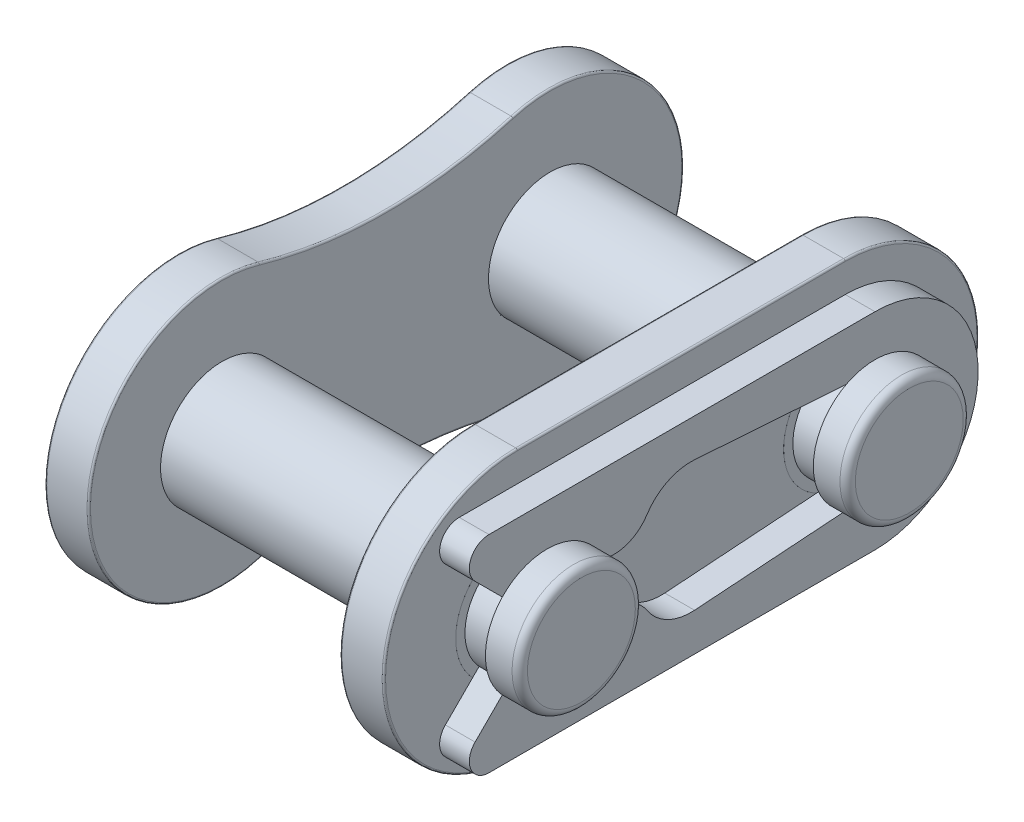
SolidWorks part; units mm, degrees
ref_plane "Front Plane" through (0, 0, 0) normal (0, 0, 1) x (1, 0, 0)
ref_plane "Top Plane" through (0, 0, 0) normal (0, 1, 0) x (1, 0, 0)
ref_plane "Right Plane" through (0, 0, 0) normal (1, 0, 0) x (0, 0, -1)
sketch "Sketch1" plane through (0, 0, 0) normal (1, 0, 0) x (0, 0, -1)
  line L0 (-4.7625, 0) -> (4.7625, 0) construction
  line L1 (-4.7625, 4.4069) -> (-4.7625, -4.4069) construction
  line L2 (4.7625, 4.4069) -> (4.7625, -4.4069) construction
  circle A0 centre (-4.7625, 0) radius 2.54 construction
  circle A1 centre (4.7625, 0) radius 2.54 construction
  circle A2 centre (-4.7625, 0) radius 1.7907 construction
  circle A3 centre (4.7625, 0) radius 1.7907 construction
  point P4 (0, 0)
  point P10 (-4.7625, 0)
  point P14 (4.7625, 0)
  dimension "For Roller Diameter" = 5.08
  dimension "Pin Diameter" = 3.5814
  dimension "For Plate Height" = 8.8138
  dimension "Pitch" = 9.525
sketch "Sketch2" plane through (0, 0, 0) normal (0, 1, 0) x (1, 0, 0)
  line L0 (-2.3812, 0) -> (2.3812, 0) construction
  line L1 (0, 4.7625) -> (6.7818, 4.7625) construction
  line L2 (0, 4.7625) -> (-5.9182, 4.7625) construction
  point P0 (-3.6513, 0)
  point P3 (0, 0)
  point P4 (3.6513, 0)
  dimension "For Roller Width" = 4.7625
  dimension "Plate Thickness" = 1.27
  dimension "Length L2" = 6.7818
  dimension "Length L1" = 5.9182
sketch "Sketch3" plane through (0, 0, 0) normal (1, 0, 0) x (0, 0, -1)
  line L0 (-4.7625, 3.8781) -> (-4.7625, -3.8781) construction
  line L1 (-4.7625, 3.8781) -> (4.7625, 3.8781)
  line L2 (-4.7625, -3.8781) -> (4.7625, -3.8781)
  arc A4 (-4.7625, 3.8781) -> (-4.7625, -3.8781) centre (-4.7625, 0) ccw
  arc A5 (4.7625, -3.8781) -> (4.7625, 3.8781) centre (4.7625, 0) ccw
  circle A8 centre (-4.7625, 0) radius 1.7907
  circle A9 centre (4.7625, 0) radius 1.7907
  circle A10 centre (-4.7625, 0) radius 1.7907 construction
  point P14 (0, 0)
  dimension "D1" = 7.7561
extrude "Boss-Extrude1" add sketch "Sketch3" along normal blind 1.27 from vertex starting at point (3.6513, 0, 0)
fillet "Fillet1" radius 0.0508 8 edges at (4.9213, 0, -8.6406) (3.6513, 0, -8.6406) (4.9213, 0, 8.6406) (3.6513, 0, 8.6406) (4.9213, 3.8781, 0) (4.9213, -3.8781, 0) (3.6513, 3.8781, 0) (3.6513, -3.8781, 0)
sketch "Sketch4" plane through (0, 0, 0) normal (1, 0, 0) x (0, 0, -1)
  line L0 (0, 3.1956) -> (0, -3.1956) construction
  line L1 (0, 3.7459) -> (0, -3.7459) construction
  circle A0 centre (-4.7625, 0) radius 1.7907
  circle A1 centre (4.7625, 0) radius 1.7907
  circle A2 centre (-4.7625, 0) radius 1.7907 construction
  circle A3 centre (4.7625, 0) radius 1.7907 construction
  arc A4 (-3.6734, 3.722) -> (-3.6734, -3.722) centre (-4.7625, 0) ccw
  arc A5 (3.6734, -3.722) -> (3.6734, 3.722) centre (4.7625, 0) ccw
  arc A6 (-4.7625, 3.8781) -> (-4.7625, -3.8781) centre (-4.7625, 0) ccw construction
  arc A7 (4.7625, -3.8781) -> (4.7625, 3.8781) centre (4.7625, 0) ccw construction
  arc A8 (-3.6734, 3.722) -> (3.6734, 3.722) centre (0, 16.2752) ccw
  arc A9 (-3.6734, -3.722) -> (3.6734, -3.722) centre (0, -16.2752) cw
  circle A10 centre (-4.7625, 0) radius 4.4069 construction
  circle A11 centre (4.7625, 0) radius 4.4069 construction
  arc A12 (-3.5623, 4.2403) -> (3.5623, 4.2403) centre (0, 16.8255) ccw construction
  arc A13 (-3.5623, -4.2403) -> (3.5623, -4.2403) centre (0, -16.8255) cw construction
  point P26 (0, 0)
  dimension "D1" = 7.4917
extrude "Boss-Extrude2" add sketch "Sketch4" against normal blind 1.27 from vertex separate body starting at point (-3.6513, 0, 0)
fillet "Fillet2" radius 0.0508 8 edges at (-4.9213, 3.1956, 0) (-4.9213, 0, -8.6406) (-4.9213, -3.1956, 0) (-3.6513, 3.1956, 0) (-3.6513, 0, -8.6406) (-3.6513, -3.1956, 0) (-4.9213, 0, 8.6406) (-3.6513, 0, 8.6406)
sketch "Sketch5" plane through (0, 0, 0) normal (1, 0, 0) x (0, 0, -1)
  circle A0 centre (-4.7625, 0) radius 1.7907
  circle A1 centre (4.7625, 0) radius 1.7907
  circle A2 centre (-4.7625, 0) radius 1.7907 construction
  circle A3 centre (4.7625, 0) radius 1.7907 construction
extrude "Boss-Extrude3" add sketch "Sketch5" along normal up to vertex (6.7818 mm away) and the other way up to vertex (5.9182 mm away) separate body up to point (6.7818, 0, -4.7625) other way up to point (-5.9182, 0, -4.7625)
fillet "Fillet3" radius 0.4477 1 edges at (-5.9182, 0, 2.9718)
fillet "Fillet4" radius 0.4477 1 edges at (-5.9182, 0, -6.5532)
sketch "Sketch6" plane through (0, 0, 0) normal (0, 1, 0) x (1, 0, 0)
  line L0 (-5.9182, -4.7625) -> (-4.9212, -4.7625) construction
  line L1 (-4.9212, -4.7625) -> (-3.6513, -4.7625) construction
  dimension "D2" = 0.9969
sketch "Sketch7" plane through (4.9213, 0, 0) normal (1, 0, 0) x (0, 0, -1)
  line L0 (4.7625, -2.9967) -> (-6.4493, -2.9967)
  line L1 (-6.8529, -2.0223) -> (-5.8723, -1.0417)
  line L2 (4.7625, 2.9967) -> (-6.4493, 2.9967)
  line L3 (-6.8529, 2.0223) -> (-5.8723, 1.0417)
  line L5 (-0.4791, 1.8923) -> (4.8687, 1.5184)
  line L6 (4.8687, -1.5184) -> (-0.4791, -1.8923)
  line L8 (4.7625, 0) -> (-4.7625, 0) construction
  line L9 (-5.8723, 1.0417) -> (-0.9254, 1.0417) construction
  arc A0 (4.7625, -2.9967) -> (4.7625, 2.9967) centre (4.7625, 0) ccw
  arc A1 (4.8687, -1.5184) -> (4.8687, 1.5184) centre (4.7625, 0) ccw
  arc A2 (-5.8723, -1.0417) -> (-3.6527, -1.0417) centre (-4.7625, 0) ccw
  arc A3 (-3.6527, 1.0417) -> (-5.8723, 1.0417) centre (-4.7625, 0) ccw
  arc A4 (-6.4493, 2.9967) -> (-6.8529, 2.0223) centre (-6.4493, 2.4259) ccw
  arc A5 (-6.4493, -2.9967) -> (-6.8529, -2.0223) centre (-6.4493, -2.4259) cw
  arc A8 (-6.987, 2.7351) -> (-6.987, -2.7351) centre (-4.7625, 0) ccw construction
  arc A9 (-3.6527, 1.0417) -> (-1.8624, 1.2019) centre (-2.8203, 1.8229) ccw
  arc A10 (-1.8624, 1.2019) -> (-0.4791, 1.8923) centre (-0.5852, 0.374) cw
  arc A11 (-3.6527, -1.0417) -> (-1.8624, -1.2019) centre (-2.8203, -1.8229) cw
  arc A12 (-1.8624, -1.2019) -> (-0.4791, -1.8923) centre (-0.5852, -0.374) ccw
  dimension "D3" = 5.9934
  dimension "D6" = 1.5221
  dimension "D7" = 1.5221
  dimension "D8" = 3.5255
  dimension "D9" = 0.5708
  dimension "D5" = 1.1416
  dimension "D2" = 4
  dimension "D10" = 45
extrude "Boss-Extrude4" add sketch "Sketch7" along normal offset from surface (0.8636 mm away) 0.9969 separate body up to face at (6.7818, 0, 2.9718)
sketch "Sketch8" plane through (4.9213, 0, 0) normal (1, 0, 0) x (0, 0, -1)
  circle A0 centre (-4.7625, 0) radius 1.7907
  circle A1 centre (-4.7625, 0) radius 1.5221
  circle A2 centre (-4.7625, 0) radius 1.7907 construction
  arc A3 (-3.6527, 1.0417) -> (-5.8723, 1.0417) centre (-4.7625, 0) ccw construction
extrude "Cut-Extrude1" cut sketch "Sketch8" along normal up to surface (0.8636 mm away) up to face at (5.7849, 0, 1.714)
sketch "Sketch9" plane through (4.9213, 0, 0) normal (1, 0, 0) x (0, 0, -1)
  circle A0 centre (4.7625, 0) radius 1.7907
  circle A1 centre (4.7625, 0) radius 1.5221
  circle A2 centre (-4.7625, 0) radius 1.7907 construction
  circle A3 centre (-4.7625, 0) radius 1.5221 construction
extrude "Cut-Extrude2" cut sketch "Sketch9" along normal up to surface (0.8636 mm away) up to face at (5.7849, 0, 1.714)
sketch "Sketch10" plane through (0, 0, 0) normal (0, 1, 0) x (1, 0, 0)
  line L0 (6.7818, -4.7625) -> (-5.9182, -4.7625) construction
  line L2 (-5.9182, -2.9718) -> (-5.9182, -6.5532) construction
  line L3 (6.7818, -2.9718) -> (6.7818, -6.5532) construction
  point P9 (-5.9182, -4.7625)
  point P10 (6.7818, -4.7625)
  dimension "D1" = 3.5814
fillet "Fillet5" radius 0.2238 1 edges at (6.7818, 0, 2.9718)
fillet "Fillet6" radius 0.2238 1 edges at (6.7818, 0, -6.5532)
ref_plane "Plane1" through (0, 0, 0) normal (1, 0, 0) x (0, 0, -1)
equation "\"D1@Sketch2\" = \"Plate Thickness@Sketch2\""
equation "\"D1@Fillet1\" = \"Plate Thickness@Sketch2\" * .04"
equation "\"D1@Boss-Extrude1\"=\"Plate Thickness@Sketch2\""
equation "\"D1@Sketch3\" = \"For Plate Height@Sketch1\" * .88"
equation "\"D1@Sketch4\" = \"For Plate Height@Sketch1\" * .85"
equation "\"D1@Boss-Extrude2\"=\"Plate Thickness@Sketch2\""
equation "\"D1@Fillet2\"=\"D1@Fillet1\""
equation "\"D1@Fillet3\"=\"Pin Diameter@Sketch1\"*.125"
equation "\"D1@Fillet4\"=\"D1@Fillet3\""
equation "\"D1@Sketch6\" = \"Plate Thickness@Sketch2\""
equation "\"D1@Boss-Extrude4\"=\"D2@Sketch6\""
equation "\"D6@Sketch7\"=(\"Pin Diameter@Sketch1\"/2)*.85"
equation "\"D7@Sketch7\"=\"D6@Sketch7\""
equation "\"D3@Sketch7\"=\"For Plate Height@Sketch1\"*.68"
equation "\"D8@Sketch7\"=(\"For Plate Height@Sketch1\"/2)*.8"
equation "\"D9@Sketch7\"=\"D5@Sketch7\"/2"
equation "\"D1@Fillet6\"=\"D1@Fillet5\""
equation "\"D1@Fillet5\"=\"D1@Fillet3\"*.5"
equation "\"D5@Sketch7\"=\"D7@Sketch7\"*.75"
equation "\"D1@Sketch10\"=\"Pin Diameter@Sketch1\""
